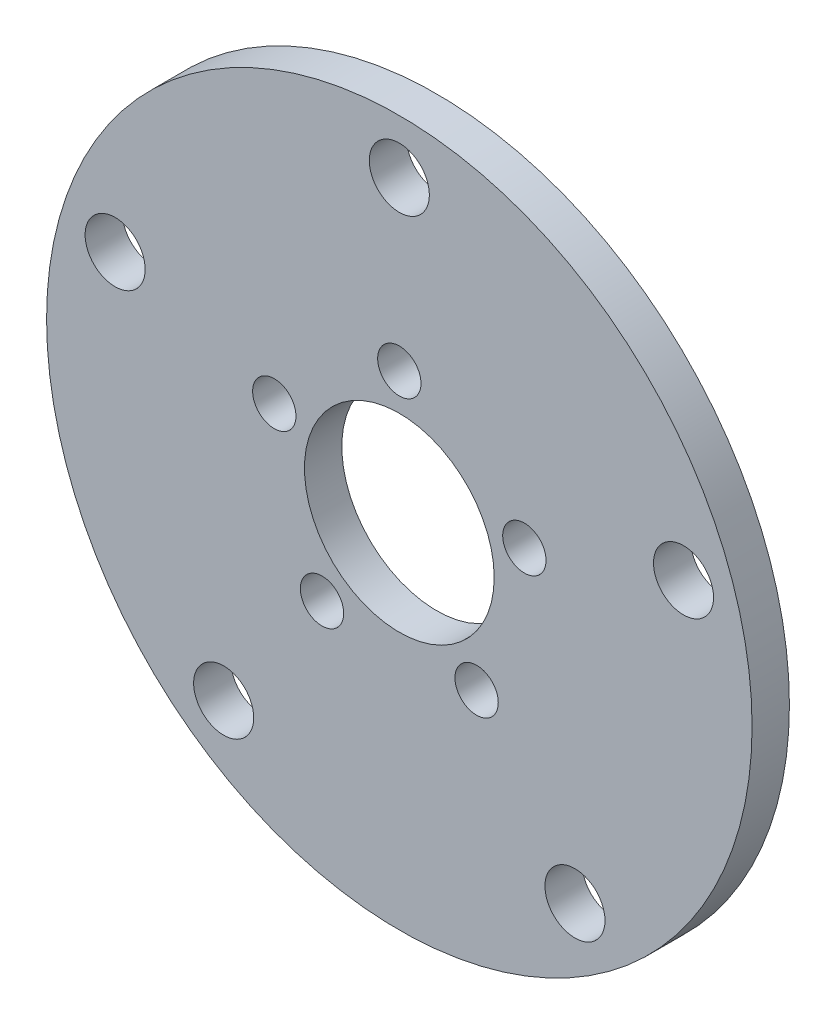
SolidWorks part; units mm, degrees
ref_plane "Front Plane" through (0, 0, 0) normal (0, 0, 1) x (1, 0, 0)
ref_plane "Top Plane" through (0, 0, 0) normal (0, 1, 0) x (1, 0, 0)
ref_plane "Right Plane" through (0, 0, 0) normal (1, 0, 0) x (0, 0, -1)
sketch "Sketch1" plane through (0, 0, 0) normal (0, 0, 1) x (1, 0, 0)
  line L0 (0, 0) -> (0, 11.176) construction
  line L1 (0, 25.4) -> (0, 0) construction
  circle A0 centre (0, 0) radius 29.9847
  circle A1 centre (0, 0) radius 8.0645
  circle A2 centre (0, 11.176) radius 1.8415
  circle A3 centre (0, 25.4) radius 2.5527
  circle A4 centre (10.629, 3.4536) radius 1.8415
  circle A5 centre (24.1568, 7.849) radius 2.5527
  circle A6 centre (6.5691, -9.0416) radius 1.8415
  circle A7 centre (14.9297, -20.549) radius 2.5527
  circle A8 centre (-6.5691, -9.0416) radius 1.8415
  circle A9 centre (-14.9297, -20.549) radius 2.5527
  circle A10 centre (-10.629, 3.4536) radius 1.8415
  circle A11 centre (-24.1568, 7.849) radius 2.5527
  circle A12 centre (0, 0) radius 29.9847 construction
  dimension "D2" = 16.129
  dimension "D4" = 3.683
  dimension "D5" = 5.1054
  dimension "D3" = 11.176
  dimension "D6" = 25.4
  dimension "D7" = 5
extrude "Boss-Extrude1" add sketch "Sketch1" along normal blind 3.175
